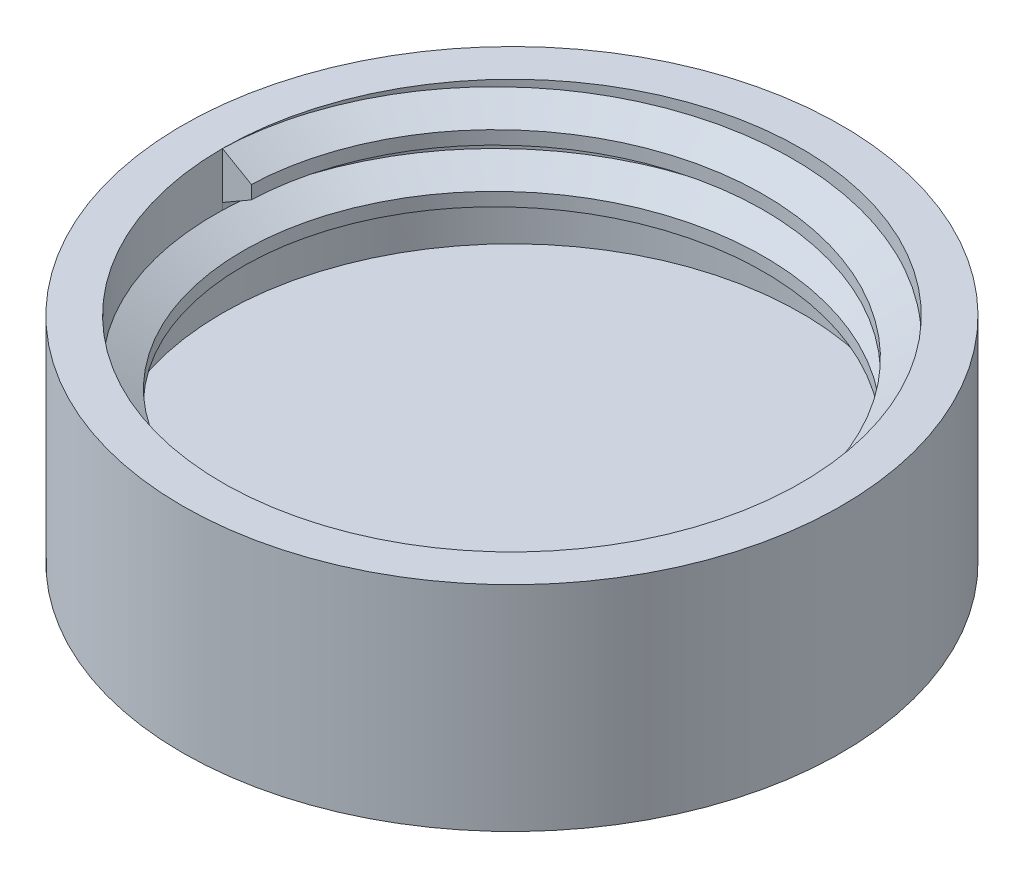
SolidWorks part; units mm, degrees
ref_plane "Front Plane" through (0, 0, 0) normal (0, 0, 1) x (1, 0, 0)
ref_plane "Top Plane" through (0, 0, 0) normal (0, 1, 0) x (1, 0, 0)
ref_plane "Right Plane" through (0, 0, 0) normal (1, 0, 0) x (0, 0, -1)
sketch "Sketch1" plane through (0, 0, 0) normal (0, 1, 0) x (1, 0, 0)
  circle A0 centre (0, 0) radius 37
  dimension "D1" = 74
extrude "Boss-Extrude1" add sketch "Sketch1" along normal blind 8
sketch "Sketch2" plane through (0, 8, 0) normal (0, 1, 0) x (1, 0, 0)
  circle A0 centre (0, 0) radius 37
  circle A1 centre (0, 0) radius 32.5
  circle A2 centre (0, 0) radius 37 construction
  dimension "D1" = 65
extrude "Boss-Extrude2" add sketch "Sketch2" along normal blind 16
thread "Thread1" pitch 6 method extrude profile "Thread Profile1" start angle 0, offset 0, length 10, pitch 6, diameter 65
ref_plane "Plane1" through (-32.5, 24, 0) normal (0, 0, 1) x (-1, 0, 0)
sketch "Thread Profile1" plane through (-32.5, 24, 0) normal (0, 0, 1) x (-1, 0, 0)
  line L0 (0, 0) -> (0, 6) construction
  line L11 (0, 0) -> (0, 5.25)
  line L12 (0, 5.25) -> (-3.2476, 3.375)
  line L13 (-3.2476, 3.375) -> (-3.2476, 1.875)
  line L15 (-3.2476, 1.875) -> (0, 0)
  line L17 (-3.2476, 2.625) -> (0, 2.625) construction
  point P2 (0, 0)
  dimension "Pitch" = 6
  dimension "Profile_Angle" = 60
  dimension "Profile_Land" = 1.5
  dimension "Profile_Height" = 3.2476
